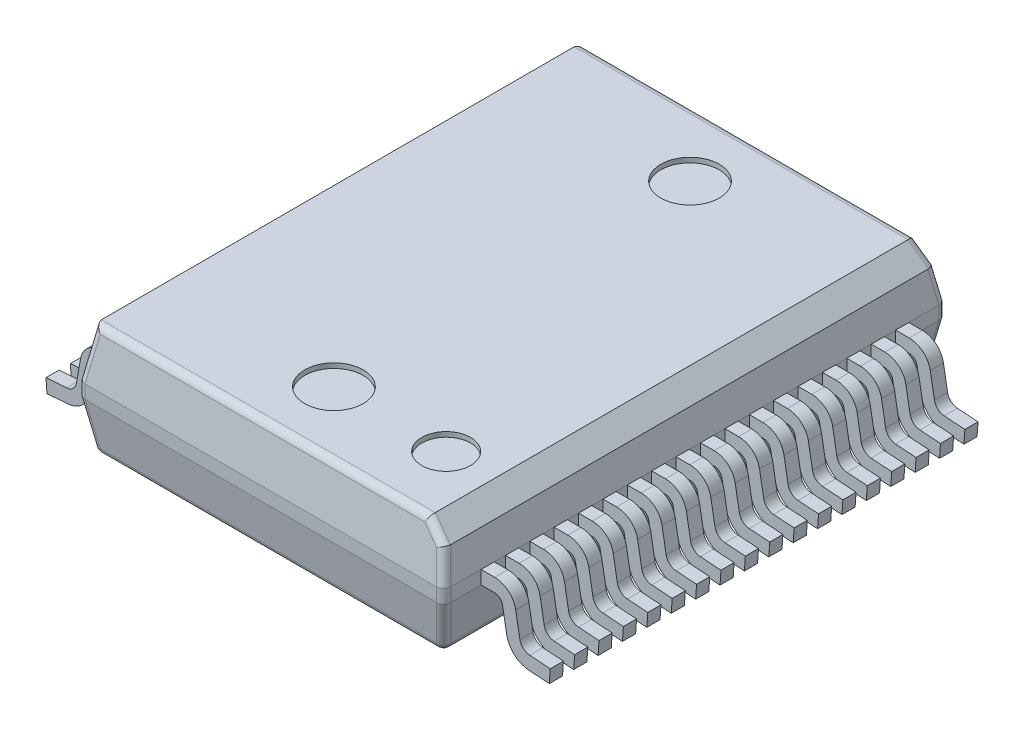
SolidWorks part; units mm, degrees
other "case"
ref_plane "Front Plane" through (0, 0, 0) normal (0, 0, 1) x (1, 0, 0)
ref_plane "Top Plane" through (0, 0, 0) normal (0, 1, 0) x (1, 0, 0)
ref_plane "Right Plane" through (0, 0, 0) normal (1, 0, 0) x (0, 0, -1)
ref_plane "case bottom" through (0, 0.05, 0) normal (0, 1, 0) x (1, 0, 0)
sketch "Sketch1" plane through (0, 0.05, 0) normal (0, -1, 0) x (-1, 0, 0)
  line L0 (-3.75, -5.15) -> (3.75, -5.15)
  line L1 (3.75, -5.15) -> (3.75, 5.15)
  line L2 (3.75, 5.15) -> (-3.75, 5.15)
  line L3 (-3.75, 5.15) -> (-3.75, -5.15)
  point P5 (-3.75, 0)
  point P6 (0, 5.15)
  dimension "D1" = 7.5
  dimension "D2" = 10.3
extrude "Boss-Extrude1" add sketch "Sketch1" against normal blind 2.28
ref_plane "Plane1" through (0, 1.19, 0) normal (0, 1, 0) x (1, 0, 0)
ref_plane "Plane2" through (0, 1.0525, 0) normal (0, 1, 0) x (1, 0, 0)
sketch "Sketch2" plane through (0, 0, 0) normal (1, 0, 0) x (0, 0, -1)
  line L0 (-5.15, 1.0525) -> (-4.9732, 0.05)
  line L1 (4.125, 1.0525) -> (-4.125, 1.0525) construction
  line L2 (-4.9732, 0.05) -> (-5.15, 0.05)
  line L3 (-5.15, 0.05) -> (-5.15, 1.0525)
  line L4 (0, -1000) -> (0, 49000) construction
  line L5 (-5.15, 2.33) -> (-5.15, 0.05) construction
  line L6 (5.15, 0.05) -> (-5.15, 0.05) construction
  line L7 (4.9732, 0.05) -> (5.15, 0.05)
  line L8 (5.15, 1.0525) -> (4.9732, 0.05)
  line L9 (5.15, 0.05) -> (5.15, 1.0525)
  line L10 (-1005.6111, 1.19) -> (48994.3889, 1.19) construction
  line L12 (4.125, 1.19) -> (-4.125, 1.19) construction
  line L13 (-4.9732, 2.33) -> (-5.15, 2.33)
  line L14 (-5.15, 1.3275) -> (-4.9732, 2.33)
  line L15 (-5.15, 2.33) -> (-5.15, 1.3275)
  line L16 (4.9732, 2.33) -> (5.15, 2.33)
  line L17 (5.15, 1.3275) -> (4.9732, 2.33)
  line L18 (5.15, 2.33) -> (5.15, 1.3275)
  dimension "D1" = 10
  dimension "D2" = 0.275
sketch "Sketch3" plane through (0, 0, 0) normal (0, 0, 1) x (1, 0, 0)
  line L0 (-3.75, 1.0525) -> (-3.5732, 0.05)
  line L1 (4.125, 1.19) -> (-4.125, 1.19) construction
  line L2 (-3.5732, 0.05) -> (-3.75, 0.05)
  line L3 (-3.75, 0.05) -> (-3.75, 1.0525)
  line L4 (0, -971.2202) -> (0, 48304.0325) construction
  line L5 (3.75, 0.05) -> (-3.75, 0.05) construction
  line L6 (4.125, 1.0525) -> (-4.125, 1.0525) construction
  line L7 (-3.75, 2.33) -> (-3.75, 0.05) construction
  line L8 (-3.5732, 2.33) -> (-3.75, 2.33)
  line L9 (-3.75, 1.3275) -> (-3.5732, 2.33)
  line L10 (-1005.6111, 1.19) -> (48994.3889, 1.19) construction
  line L11 (-3.75, 2.33) -> (-3.75, 1.3275)
  line L12 (3.5732, 0.05) -> (3.75, 0.05)
  line L13 (3.75, 1.0525) -> (3.5732, 0.05)
  line L14 (3.75, 0.05) -> (3.75, 1.0525)
  line L15 (3.5732, 2.33) -> (3.75, 2.33)
  line L16 (3.75, 1.3275) -> (3.5732, 2.33)
  line L17 (3.75, 2.33) -> (3.75, 1.3275)
  dimension "D1" = 10
extrude "Cut-Extrude1" cut sketch "Sketch2" against normal through all and the other way through all
extrude "Cut-Extrude2" cut sketch "Sketch3" against normal through all and the other way through all
sketch "Sketch6" plane through (0, 2.33, 0) normal (0, 1, 0) x (1, 0, 0)
  line L0 (0, -1000) -> (0, 49000) construction
  line L1 (-1000, 0) -> (49000, 0) construction
  circle A0 centre (0, -3.65) radius 0.6
  circle A1 centre (2.3, -3.65) radius 0.5
  circle A2 centre (0, 3.65) radius 0.6
  dimension "D1" = 1.2
  dimension "D2" = 1
  dimension "D3" = 3.65
  dimension "D4" = 2.3
extrude "Cut-Extrude3" cut sketch "Sketch6" against normal blind 0.1
chamfer "Chamfer1" distance 0.3 angle 45 1 edges at (3.5732, 2.33, 0) first distance on face at (0, 2.33, -4.25)
sketch "Sketch8" plane through (0, 0.05, 0) normal (0, -1, 0) x (1, 0, 0)
  line L0 (-1000, 0) -> (49000, 0) construction
  line L1 (0, -1000) -> (0, 49000) construction
  circle A0 centre (2.9, 4.3) radius 0.4
  circle A1 centre (0, 4.3) radius 0.4
  circle A2 centre (0, -4.3) radius 0.4
  dimension "D1" = 0.8
  dimension "D2" = 4.3
  dimension "D3" = 2.9
extrude "Cut-Extrude4" cut sketch "Sketch8" against normal blind 0.1
fillet "Fillet1" radius 0.15 20 edges at (-3.5732, 0.05, 0) (0, 0.05, -4.9732) (-3.6616, 0.5513, -5.0616) (-3.75, 1.19, -5.15) (-3.6616, 1.8288, -5.0616) (-0.15, 2.33, -4.9732) (3.4553, 2.1479, -5.0053) (3.6937, 1.6466, -5.0937) (3.75, 1.19, -5.15) (3.6616, 0.5513, -5.0616) (-3.6616, 1.8288, 5.0616) (-3.75, 1.19, 5.15) (-3.6616, 0.5513, 5.0616) (3.5732, 0.05, 0) (0, 0.05, 4.9732) (-0.15, 2.33, 4.9732) (3.4553, 2.1479, 5.0053) (3.6937, 1.6466, 5.0937) (3.75, 1.19, 5.15) (3.6616, 0.5513, 5.0616)
sketch "Sketch14" plane through (0, 0.05, 0) normal (0, -1, 0) x (1, 0, 0)
  line L0 (0, -1000) -> (0, 49000) construction
  line L1 (-1000, 0) -> (49000, 0) construction
  line L2 (2.35, 3.65) -> (0.55, 3.65)
  line L3 (-2.35, 3.65) -> (-0.55, 3.65)
  line L4 (-2.5, 3.5) -> (-2.5, 0.55)
  line L5 (-2.35, 0.4) -> (-0.55, 0.4)
  line L6 (-0.4, 3.5) -> (-0.4, 0.55)
  line L7 (-2.5, 3.65) -> (-0.4, 0.4) construction
  line L8 (-2.5, 0.4) -> (-0.4, 3.65) construction
  line L9 (2.325, -0.4) -> (-2.325, -0.4)
  line L10 (2.475, -0.55) -> (2.475, -3.5)
  line L11 (2.325, -3.65) -> (-2.325, -3.65)
  line L12 (-2.475, -0.55) -> (-2.475, -3.5)
  line L13 (2.475, -0.4) -> (-2.475, -3.65) construction
  line L14 (2.475, -3.65) -> (-2.475, -0.4) construction
  line L15 (0.4, 3.5) -> (0.4, 0.55)
  line L16 (2.35, 0.4) -> (0.55, 0.4)
  line L17 (2.5, 3.5) -> (2.5, 0.55)
  arc A0 (-2.325, -3.65) -> (-2.475, -3.5) centre (-2.325, -3.5) cw
  arc A1 (2.475, -3.5) -> (2.325, -3.65) centre (2.325, -3.5) cw
  arc A2 (2.325, -0.4) -> (2.475, -0.55) centre (2.325, -0.55) cw
  arc A3 (-2.325, -0.4) -> (-2.475, -0.55) centre (-2.325, -0.55) ccw
  arc A4 (-2.5, 0.55) -> (-2.35, 0.4) centre (-2.35, 0.55) ccw
  arc A5 (-0.55, 0.4) -> (-0.4, 0.55) centre (-0.55, 0.55) ccw
  arc A6 (-0.55, 3.65) -> (-0.4, 3.5) centre (-0.55, 3.5) cw
  arc A7 (-2.35, 3.65) -> (-2.5, 3.5) centre (-2.35, 3.5) ccw
  arc A8 (2.35, 3.65) -> (2.5, 3.5) centre (2.35, 3.5) cw
  arc A9 (0.55, 3.65) -> (0.4, 3.5) centre (0.55, 3.5) ccw
  arc A10 (0.55, 0.4) -> (0.4, 0.55) centre (0.55, 0.55) cw
  arc A11 (2.5, 0.55) -> (2.35, 0.4) centre (2.35, 0.55) cw
  point P4 (-1.45, 2.025)
  point P10 (0, -2.025)
  dimension "D8" = 0.15
  dimension "D1" = 3.25
  dimension "D2" = 2.1
  dimension "D3" = 3.25
  dimension "D4" = 4.95
  dimension "D5" = 0.4
  dimension "D6" = 0.4
  dimension "D7" = 0.4
extrude "Boss-Extrude2" add sketch "Sketch14" along normal blind 0.05 separate body
ref_plane "Plane3" through (5.15, 0, 0) normal (1, 0, 0) x (0, 0, -1)
ref_plane "Plane4" through (0, 0, 4.25) normal (0, 0, 1) x (1, 0, 0)
sketch "Sketch9" plane through (5.15, 0, 0) normal (1, 0, 0) x (0, 0, -1)
  line L0 (-1006.7045, 0) -> (48993.2955, 0) construction
  line L1 (4.125, 0) -> (-4.125, 0) construction
sketch "Sketch10" plane through (3.75, 0, 0) normal (1, 0, 0) x (0, 0, -1)
  line L0 (-1007.523, 1.19) -> (48992.477, 1.19) construction
  line L1 (-4.25, -995.4686) -> (-4.25, 49004.5314) construction
  line L2 (-4.25, 1.254) -> (-4.25, -1.254) construction
  line L3 (4.125, 1.19) -> (-4.125, 1.19) construction
  line L5 (-4.385, 1.0525) -> (-4.115, 1.0525)
  line L6 (-4.385, 1.0525) -> (-4.385, 1.3275)
  line L7 (-4.385, 1.3275) -> (-4.115, 1.3275)
  line L8 (-4.115, 1.0525) -> (-4.115, 1.3275)
  line L9 (-4.385, 1.0525) -> (-4.115, 1.3275) construction
  line L10 (-4.385, 1.3275) -> (-4.115, 1.0525) construction
  line L11 (5, 1.3275) -> (-5, 1.3275) construction
  point P8 (-4.25, 1.19)
  dimension "D1" = 0.275
  dimension "D2" = 0.27
sketch "Sketch11" plane through (0, 0, 4.25) normal (0, 0, 1) x (1, 0, 0)
  line L0 (-1001.0149, 0) -> (48998.9851, 0) construction
  line L1 (4.125, 0) -> (-4.125, 0) construction
  line L2 (5.15, 0) -> (3492.9737, 49878.2025) construction
  line L3 (5.15, -1000) -> (5.15, 49000) construction
  line L4 (5.1692, 0.2743) -> (5.15, 0) construction
  line L5 (5.1596, 0.1372) -> (4.7385, 0.1666)
  line L6 (3.75, 1.19) -> (4.03, 1.19)
  line L7 (4.3254, 0.9421) -> (4.41, 0.4624)
  line L8 (3.75, 1.0525) -> (4.03, 1.0525) construction
  line L9 (4.19, 0.9182) -> (4.2746, 0.4385) construction
  line L10 (5.15, 0) -> (4.7289, 0.0294) construction
  line L11 (3.75, 1.3275) -> (4.03, 1.3275) construction
  line L12 (4.4609, 0.966) -> (4.5454, 0.4862) construction
  line L13 (5.1692, 0.2743) -> (4.7481, 0.3038) construction
  arc A0 (4.03, 1.19) -> (4.3254, 0.9421) centre (4.03, 0.89) cw
  arc A1 (4.7385, 0.1666) -> (4.41, 0.4624) centre (4.7635, 0.5247) cw
  arc A2 (4.03, 1.0525) -> (4.19, 0.9182) centre (4.03, 0.89) cw construction
  arc A3 (4.7289, 0.0294) -> (4.2746, 0.4385) centre (4.7635, 0.5247) cw construction
  arc A4 (4.03, 1.3275) -> (4.4609, 0.966) centre (4.03, 0.89) cw construction
  arc A5 (4.7481, 0.3038) -> (4.5454, 0.4862) centre (4.7635, 0.5247) cw construction
  point P0 (3.75, 1.19)
  point P6 (5.15, 0)
  point P14 (5.1596, 0.1372)
  point P19 (4.35, 0.25)
  dimension "D5" = 0.3
  dimension "D1" = 4
  dimension "D2" = 0.275
  dimension "D3" = 0.25
  dimension "D4" = 0.8
  dimension "D9" = 100
  dimension "D10" = 0.28
  dimension "D7" = 0.1375
  dimension "D8" = 0.1375
sweep "Sweep1" add profiles "Sketch10" path "Sketch11"
pattern_linear "LPattern1" count 18 spacing 0.5 along (0, 0, -1) of bodies 108
mirror "Mirror1" about plane through (0, 0, 0) normal (1, 0, 0) of bodies 108 109 110 111 112 113 114 115 116 117 118 119 120 121 122 123 124 125
other "Freeze***"
